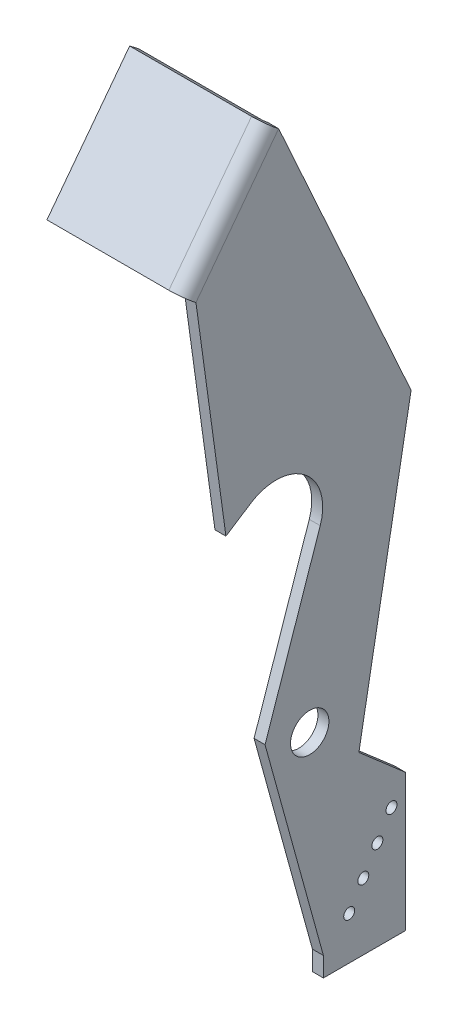
SolidWorks part; units mm, degrees
note: The reader was unsure of these and kept them because the rebuilt part matched: flange length of "Ребро-кромка1".
ref_plane "Спереди" through (0, 0, 0) normal (0, 0, 1) x (1, 0, 0)
ref_plane "Сверху" through (0, 0, 0) normal (0, 1, 0) x (1, 0, 0)
ref_plane "Справа" through (0, 0, 0) normal (1, 0, 0) x (0, 0, -1)
sketch "Эскиз6" plane through (0, 0, 0) normal (1, 0, 0) x (0, 0, -1)
  line L0 (-41.5156, 156.6399) -> (-30.5709, 77.3245)
  line L1 (-12.25, 68.9198) -> (0, 0) construction
  line L2 (-16.3, 4.2846) -> (5, -72.9877)
  line L4 (35, -30.1093) -> (17.9522, -15.2867)
  line L7 (-11.3251, 196.4963) -> (-41.5156, 156.6399)
  line L8 (-21.4732, 83.2003) -> (-30.5709, 77.3245)
  line L9 (-200, 0) -> (0, 0) construction
  line L10 (35, -30.1093) -> (5, -80.1093) construction
  line L11 (37, 15) -> (93.9306, 15) construction
  line L12 (37, 15) -> (37, -15) construction
  line L14 (93.9306, 15) -> (93.9306, -15) construction
  line L16 (5, -72.9877) -> (5, -80.1093)
  line L17 (5, -80.1093) -> (35, -80.1093)
  line L18 (35, -30.1093) -> (35, -80.1093)
  line L19 (3.8427, 63.4402) -> (-16.3, 4.2846)
  line L20 (17.9522, -15.2867) -> (37, 89.6651)
  line L21 (37, 89.6651) -> (-11.3251, 196.4963)
  circle A0 centre (0, 0) radius 5 construction
  circle A1 centre (-200, 0) radius 5 construction
  arc A2 (3.8427, 63.4402) -> (-0.5205, 56.6145) centre (-12.25, 68.9198) ccw construction
  circle A3 centre (-56.25, 139.0537) radius 17 construction
  arc A4 (-21.4732, 83.2003) -> (3.8427, 63.4402) centre (-12.25, 68.9198) cw
  circle A6 centre (0, 0) radius 7
  circle A7 centre (29.855, -38.6842) radius 2
  circle A8 centre (24.7101, -47.2591) radius 2
  circle A10 centre (19.5651, -55.8341) radius 2
  circle A11 centre (14.4202, -64.409) radius 2
  point P12 (37, 0)
  dimension "D1" = 34
  dimension "D2" = 10
  dimension "D3" = 10
  dimension "D7" = 200
  dimension "D20" = 14
  dimension "D22" = 4
  dimension "D4" = 200
  dimension "D5" = 200
  dimension "D6" = 70
  dimension "D8" = 150
  dimension "D9" = 65
  dimension "D13" = 37
  dimension "D14" = 2
  dimension "D15" = 30
  dimension "D16" = 50
  dimension "D17" = 45
  dimension "D21" = 50
  dimension "D23" = 10
  dimension "D24" = 10
  dimension "D25" = 10
  dimension "D26" = 10
base flange "Базовая кромка2" sketch "Эскиз6" thickness 4 reverse thickness direction no parameters "D1"=1.5
edge flange "Ребро-кромка1" sketch "Эскиз15" flange angle 90 flange length 50 flange position bend outside bend radius 1.5 thickness 4 parameters "D6"=10
sketch "Эскиз15" plane through (-4, 77.0911, 101.7726) normal (0, 0.6038, 0.7971) x (0, 0.7971, -0.6038)
  line L2 (149.7944, 0) -> (149.7944, 46)
  line L3 (149.7944, 46) -> (99.7944, 46)
  line L4 (99.7944, 46) -> (99.7944, 0)
  line L9 (149.7944, 0) -> (99.7944, 0) construction
  line L10 (149.7944, 0) -> (99.7944, 0)
bend "EdgeBend1" bend radius 1.5 bend angle 90 parameters "D5"=1
sketch "Сгиб-Линии3" [suppressed] plane through (0, 0, 0) normal (0, 1, 0) x (1, 0, 0)
sketch "Граничная рамка3" [suppressed] plane through (0, 0, 0) normal (0, 1, 0) x (1, 0, 0)
sketch "Эскиз16" [suppressed] plane through (0, 0, 0) normal (1, 0, 0) x (0, 0, -1)
  circle A0 centre (-43.7069, 158.2997) radius 2
  circle A1 centre (-13.5163, 198.1561) radius 2
  dimension "D1" = 4
extrude "Вырез-Вытянуть1" [suppressed] cut sketch "Эскиз16" against normal blind 10
sheet metal parameters "Листовой металл4" thickness 4 parameters "D1"=1.5
flat pattern "Развертка4" [suppressed]
sketch "Сгиб-Линии4" plane through (0, 0, 0) normal (0, 1, 0) x (1, 0, 0)
sketch "Граничная рамка4" [suppressed] plane through (0, 0, 0) normal (0, 1, 0) x (1, 0, 0)
sheet metal parameters "Листовой металл5" thickness 4 parameters "D1"=1.5
flat pattern "Развертка4"
sketch "Сгиб-Линии4" plane through (0, 0, 0) normal (1, 0, 0) x (0, 0, -1)
  line L0 (-13.5163, 198.1561) -> (-43.7069, 158.2997) construction
  line L1 (-13.5163, 198.1561) -> (-43.7069, 158.2997) construction
sketch3d "Граничная рамка4" [suppressed]
  line L0 (20.0931, -157.8159, 0) -> (-77.9329, 145.1459, 0) construction
  line L1 (98.7866, -132.3539, 0) -> (0.7607, 170.6079, 0) construction
  line L2 (20.0931, -157.8159, 0) -> (98.7866, -132.3539, 0) construction
  line L3 (-77.9329, 145.1459, 0) -> (0.7607, 170.6079, 0) construction
bend of the flat pattern "Плоское состояние-<EdgeBend1>1"
